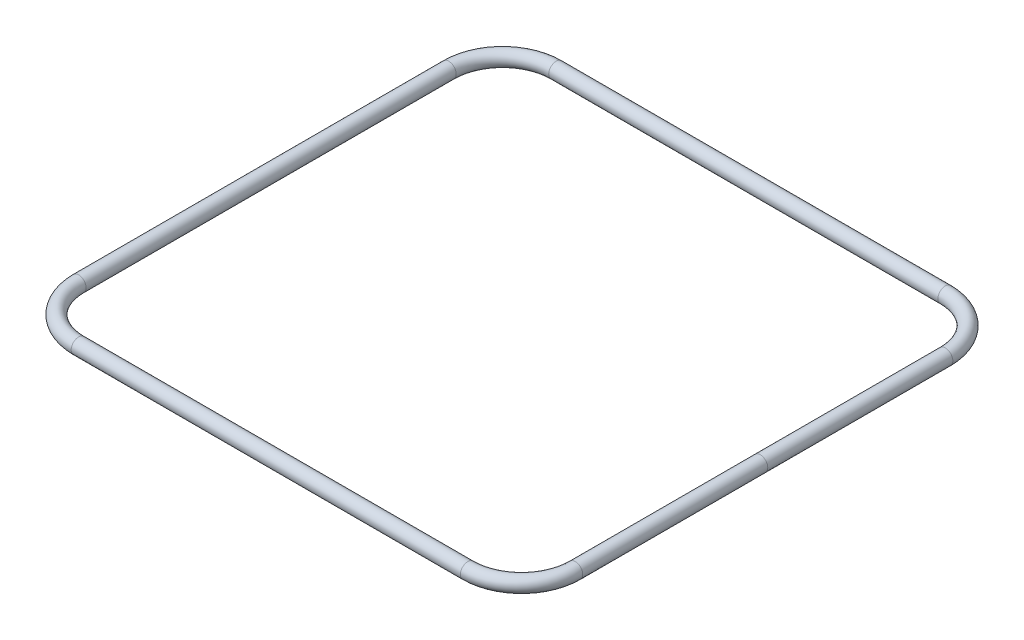
SolidWorks part; units mm, degrees
ref_plane "Front Plane" through (0, 0, 0) normal (0, 0, 1) x (1, 0, 0)
ref_plane "Top Plane" through (0, 0, 0) normal (0, 1, 0) x (1, 0, 0)
ref_plane "Right Plane" through (0, 0, 0) normal (1, 0, 0) x (0, 0, -1)
sketch "BaseDimensions" plane through (0, 0, 0) normal (0, 1, 0) x (1, 0, 0)
  line L0 (0, -63.5) -> (0, 63.5) construction
  line L1 (63.5, 0) -> (-63.5, 0) construction
  point P5 (0, 0)
  point P6 (0, 0)
  dimension "D1" = 127
  dimension "D2" = 127
sketch "O-RingPath" plane through (0, 0, 0) normal (0, 1, 0) x (1, 0, 0)
  line L0 (45.9922, -56.4388) -> (-45.9922, -56.4388)
  line L1 (58.6922, -43.7388) -> (58.6922, 43.7388)
  line L2 (0, 0) -> (0, -56.4388) construction
  line L3 (58.6922, 0) -> (0, 0) construction
  line L4 (-58.6922, -43.7388) -> (-58.6922, 43.7388)
  line L5 (45.9922, 56.4388) -> (-45.9922, 56.4388)
  arc A0 (45.9922, -56.4388) -> (58.6922, -43.7388) centre (45.9922, -43.7388) ccw
  arc A1 (-45.9922, -56.4388) -> (-58.6922, -43.7388) centre (-45.9922, -43.7388) cw
  arc A2 (-45.9922, 56.4388) -> (-58.6922, 43.7388) centre (-45.9922, 43.7388) ccw
  arc A3 (45.9922, 56.4388) -> (58.6922, 43.7388) centre (45.9922, 43.7388) cw
  point P17 (-58.6922, 0)
  dimension "D2" = 12.7
  dimension "D3" = 7.0612
sketch "O-RingProfile" plane through (0, 0, 0) normal (0, 0, 1) x (1, 0, 0)
  circle A0 centre (58.6922, 0) radius 1.7653
  dimension "D1" = 3.5306
sweep "Sweep2" add profiles "O-RingProfile" path "O-RingPath"
ref_plane "TopOfRing" through (0, 1.7653, 0) normal (0, 1, 0) x (1, 0, 0)
ref_plane "BottomOfRing" through (0, -1.7653, 0) normal (0, -1, 0) x (-1, 0, 0)
equation "\"D1@O-RingProfile\" = \"O-Ring_CS@BladderAssembly.Assembly\""
equation "\"D1@BaseDimensions\" = \"BaseLength@BladderAssembly.Assembly\""
equation "\"D2@BaseDimensions\" = \"BaseWidth@BladderAssembly.Assembly\""
equation "\"D3@O-RingPath\" = 2 * \"O-Ring_CS@BladderAssembly.Assembly\""
equation "\"O_Ring_Len\"= \"O-Ring_Len@BladderAssembly.Assembly\""
equation "\"D1@O-RingPath\"=\"O_Ring_Len\""
